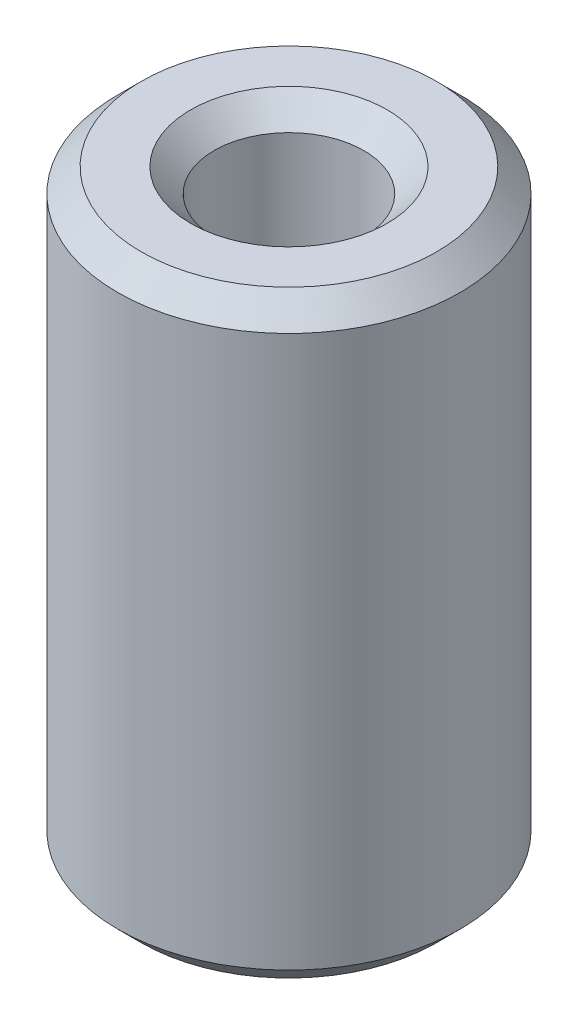
SolidWorks part; units mm, degrees
ref_plane "Front Plane" through (0, 0, 0) normal (0, 0, 1) x (1, 0, 0)
ref_plane "Top Plane" through (0, 0, 0) normal (0, 1, 0) x (1, 0, 0)
ref_plane "Right Plane" through (0, 0, 0) normal (1, 0, 0) x (0, 0, -1)
sketch "Sketch1" plane through (0, 0, 0) normal (0, 1, 0) x (1, 0, 0)
  circle A0 centre (0, 0) radius 27.5
  dimension "SLEEVE_OD" = 55
extrude "Boss-Extrude1" add sketch "Sketch1" along normal blind 96.1116
sketch "Sketch2" plane through (0, 0, 0) normal (0, 1, 0) x (1, 0, 0)
  circle A0 centre (0, 0) radius 12.024
  dimension "BORE_D" = 24.048
extrude "Cut-Extrude1" cut sketch "Sketch2" along normal through all
chamfer "Chamfer1" distance 3.7745 angle 45 4 edges at (0, 96.1116, 12.024) (0, 0, 12.024) (0, 0, 27.5) (0, 96.1116, 27.5)
